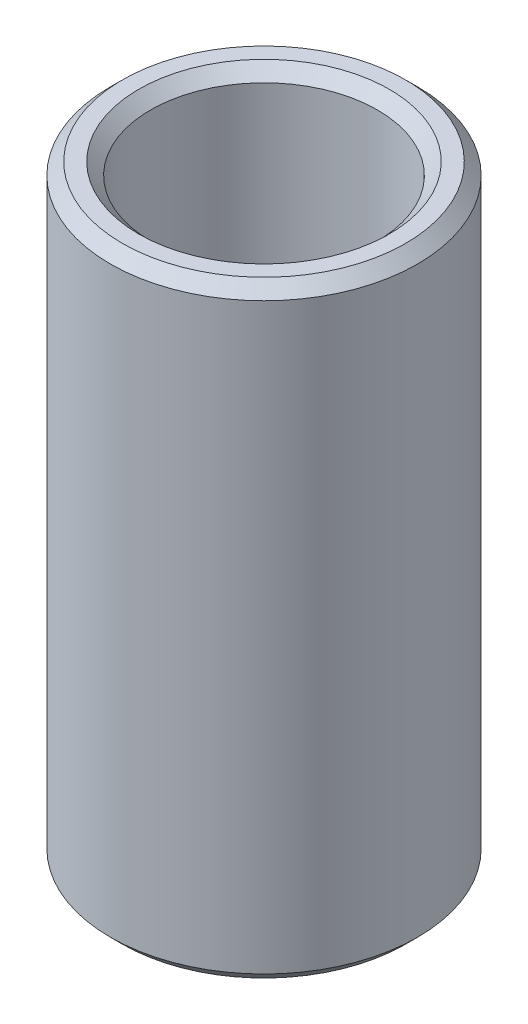
SolidWorks part; units mm, degrees
ref_plane "Front Plane" through (0, 0, 0) normal (0, 0, 1) x (1, 0, 0)
ref_plane "Top Plane" through (0, 0, 0) normal (0, 1, 0) x (1, 0, 0)
ref_plane "Right Plane" through (0, 0, 0) normal (1, 0, 0) x (0, 0, -1)
sketch "Sketch1" plane through (0, 0, 0) normal (0, 1, 0) x (1, 0, 0)
  circle A0 centre (0, 0) radius 42.5
  dimension "SLEEVE_OD" = 85
extrude "Boss-Extrude1" add sketch "Sketch1" along normal blind 167.9713
sketch "Sketch2" plane through (0, 0, 0) normal (0, 1, 0) x (1, 0, 0)
  circle A0 centre (0, 0) radius 31.3954
  dimension "BORE_D" = 62.7908
extrude "Cut-Extrude1" cut sketch "Sketch2" along normal through all
chamfer "Chamfer1" distance 3.2993 angle 45 4 edges at (0, 167.9713, 31.3954) (0, 0, 31.3954) (0, 0, 42.5) (0, 167.9713, 42.5)
